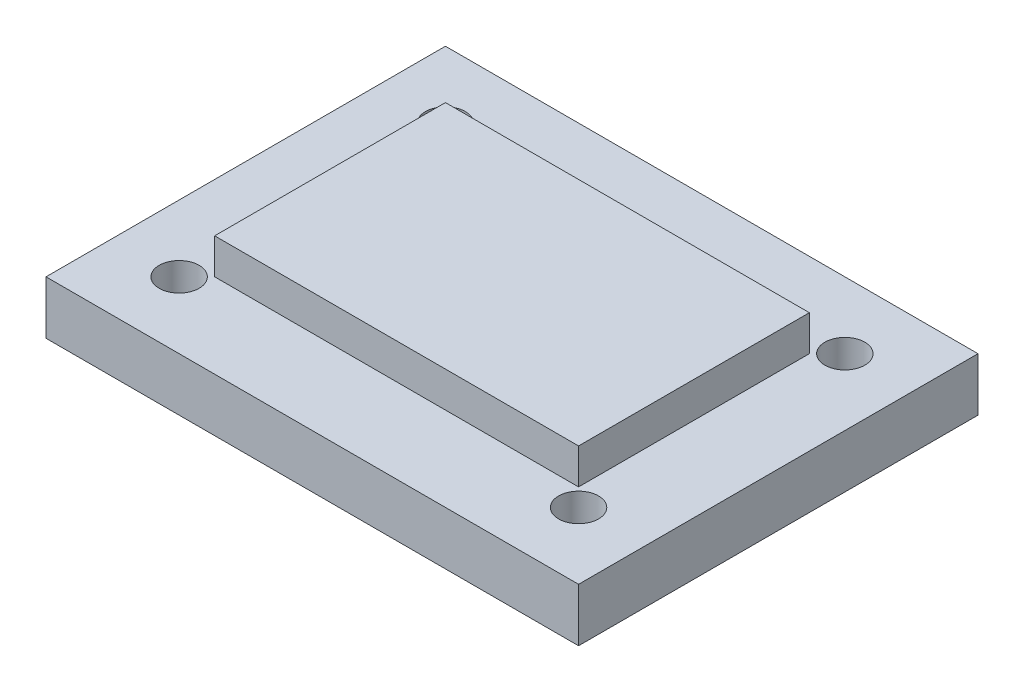
SolidWorks part; units mm, degrees
ref_plane "前视基准面" through (0, 0, 0) normal (0, 0, 1) x (1, 0, 0)
ref_plane "上视基准面" through (0, 0, 0) normal (0, 1, 0) x (1, 0, 0)
ref_plane "右视基准面" through (0, 0, 0) normal (1, 0, 0) x (0, 0, -1)
other "Configuration Table"
sketch "01_Base_Profile" plane through (0, 0, 0) normal (0, 1, 0) x (1, 0, 0)
  line L1 (-60, -45) -> (60, -45)
  line L2 (-60, -45) -> (-60, 45)
  line L3 (-60, 45) -> (60, 45)
  line L4 (60, -45) -> (60, 45)
  line L5 (-60, -45) -> (60, 45) construction
  line L6 (-60, 45) -> (60, -45) construction
  line L7 (-9, -25.5) -> (9, -25.5)
  line L8 (-9, -25.5) -> (-9, 25.5)
  line L9 (-9, 25.5) -> (9, 25.5)
  line L10 (9, -25.5) -> (9, 25.5)
  line L11 (-9, -25.5) -> (9, 25.5) construction
  line L12 (-9, 25.5) -> (9, -25.5) construction
  circle A0 centre (-45, -30) radius 4.5
  circle A1 centre (45, -30) radius 4.5
  circle A2 centre (-45, 30) radius 4.5
  circle A3 centre (45, 30) radius 4.5
  point P0 (0, 0)
  point P14 (0, 0)
extrude "01_Base_Extrude" add sketch "01_Base_Profile" along normal blind 12
sketch "02_Boss_Profile" plane through (0, 0, 0) normal (0, 1, 0) x (1, 0, 0)
  line L1 (-41, -26) -> (41, -26)
  line L2 (-41, -26) -> (-41, 26)
  line L3 (-41, 26) -> (41, 26)
  line L4 (41, -26) -> (41, 26)
  line L5 (-41, -26) -> (41, 26) construction
  line L6 (-41, 26) -> (41, -26) construction
  point P0 (0, 0)
extrude "02_Reinforcement_Boss" add sketch "02_Boss_Profile" along normal blind 20
